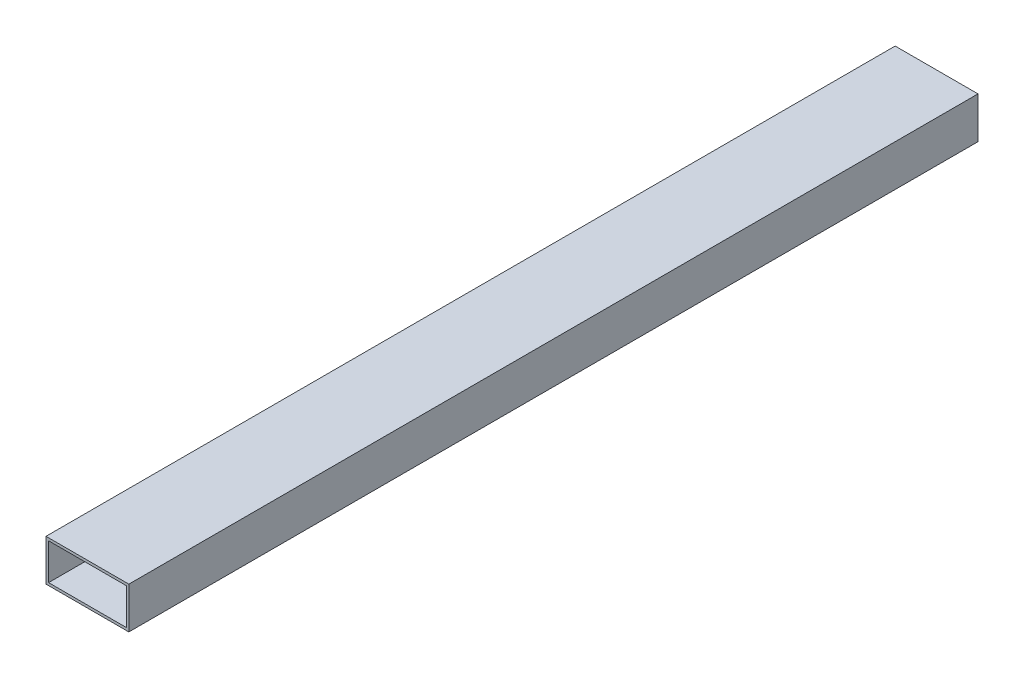
SolidWorks part; units mm, degrees
material "6061-T6 (SS)"
ref_plane "Front Plane" through (0, 0, 0) normal (0, 0, 1) x (1, 0, 0)
ref_plane "Top Plane" through (0, 0, 0) normal (0, 1, 0) x (1, 0, 0)
ref_plane "Right Plane" through (0, 0, 0) normal (1, 0, 0) x (0, 0, -1)
sketch "Sketch1" plane through (0, 0, 0) normal (0, 0, 1) x (1, 0, 0)
  line L0 (-23.8125, 11.1125) -> (23.8125, 11.1125)
  line L1 (-25.4, -12.7) -> (25.4, -12.7)
  line L2 (-25.4, -12.7) -> (-25.4, 12.7)
  line L3 (-25.4, 12.7) -> (25.4, 12.7)
  line L4 (25.4, -12.7) -> (25.4, 12.7)
  line L5 (-25.4, -12.7) -> (25.4, 12.7) construction
  line L6 (-25.4, 12.7) -> (25.4, -12.7) construction
  line L7 (23.8125, -11.1125) -> (23.8125, 11.1125)
  line L8 (-23.8125, -11.1125) -> (23.8125, -11.1125)
  line L9 (-23.8125, -11.1125) -> (-23.8125, 11.1125)
  point P0 (0, 0)
  dimension "D1" = 50.8
  dimension "D2" = 25.4
  dimension "D3" = 1.5875
extrude "Boss-Extrude1" add sketch "Sketch1" along normal mid plane 520.7
